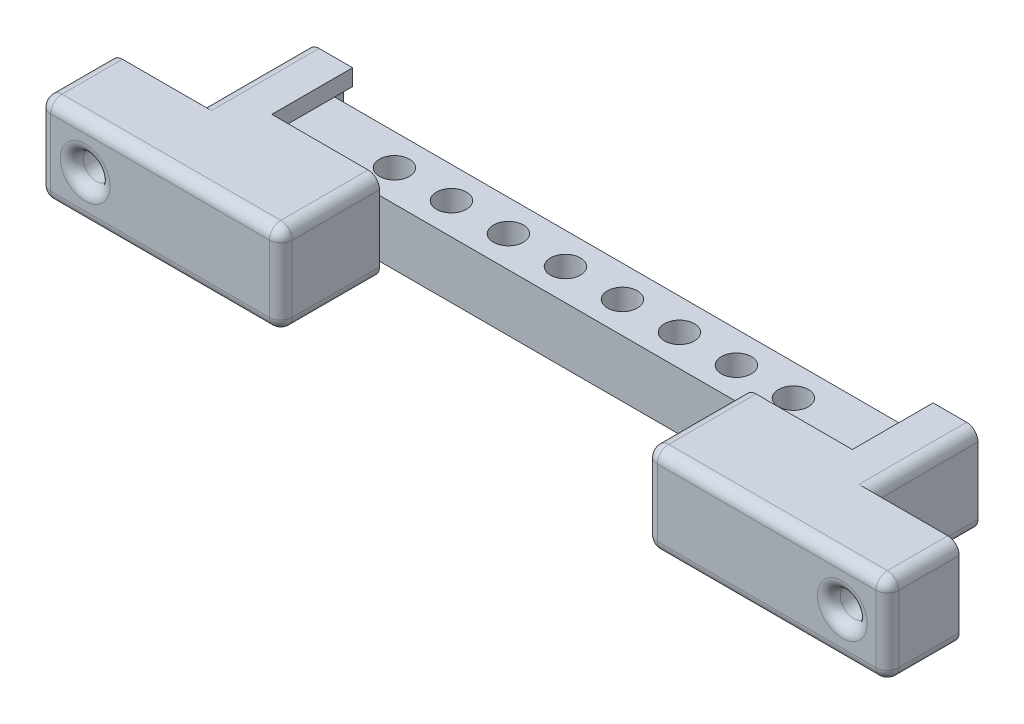
SolidWorks part; units mm, degrees
ref_plane "Front Plane" through (0, 0, 0) normal (0, 0, 1) x (1, 0, 0)
ref_plane "Top Plane" through (0, 0, 0) normal (0, 1, 0) x (1, 0, 0)
ref_plane "Right Plane" through (0, 0, 0) normal (1, 0, 0) x (0, 0, -1)
sketch "Sketch1" plane through (0, 0, 0) normal (0, 1, 0) x (1, 0, 0)
  line L0 (47.244, 0) -> (-47.244, 0)
  line L5 (-47.244, 0) -> (-47.244, 8)
  line L6 (-47.244, 8) -> (-37.338, 8)
  line L7 (-37.338, 8) -> (-37.338, 20)
  line L8 (-37.338, 20) -> (-32.338, 20)
  line L9 (-32.338, 20) -> (-32.338, 11)
  line L10 (-32.338, 11) -> (32.338, 11)
  line L11 (0, 0) -> (0, 11) construction
  line L12 (0, 0) -> (0, 22.1755) construction
  line L13 (32.338, 20) -> (32.338, 11)
  line L14 (37.338, 20) -> (32.338, 20)
  line L15 (37.338, 8) -> (37.338, 20)
  line L16 (47.244, 8) -> (37.338, 8)
  line L17 (47.244, 0) -> (47.244, 8)
  dimension "D1" = 94.488
  dimension "D2" = 8
  dimension "D3" = 9.906
  dimension "D4" = 20
  dimension "D5" = 3
  dimension "D6" = 5
extrude "Boss-Extrude1" add sketch "Sketch1" along normal mid plane 10
sketch "Sketch2" plane through (0, 0, -11) normal (0, 0, -1) x (-1, 0, 0)
  line L0 (-32.338, 5) -> (32.338, 5) construction
  line L1 (-20.338, 5) -> (20.338, 5)
  line L2 (-20.338, 5) -> (-20.338, -5)
  line L3 (-20.338, -5) -> (20.338, -5)
  line L4 (20.338, 5) -> (20.338, -5)
  line L5 (-32.338, -5) -> (32.338, -5) construction
  line L6 (-32.338, 5) -> (-32.338, -5) construction
  line L7 (32.338, 5) -> (32.338, -5) construction
  dimension "D1" = 12
  dimension "D2" = 12
extrude "Cut-Extrude1" cut sketch "Sketch2" against normal through all
sketch "Sketch3" plane through (0, 0, -8) normal (0, 0, -1) x (-1, 0, 0)
  circle A0 centre (-42.2273, 0) radius 1.5
  circle A1 centre (42.1322, 0) radius 1.5
  circle A2 centre (-42.2273, 0) radius 3.5
  circle A3 centre (42.1322, 0) radius 3.5
  dimension "D1" = 3
  dimension "D2" = 2
extrude "Cut-Extrude2" cut sketch "Sketch3" against normal through all contours A1 | A0 region at (42.2273, 0, -8) region at (-42.1322, 0, -8)
extrude "Cut-Extrude3" cut sketch "Sketch3<3>" against normal blind 3 contours A2 A0 | A3 region at (45.6284, 0, -8)
sketch "Sketch3<3>" plane through (0, 0, -8) normal (0, 0, -1) x (-1, 0, 0) same geometry as "Sketch3"
sketch "Sketch5" plane through (0, 0, -20) normal (0, 0, -1) x (-1, 0, 0)
  line L0 (-32.338, 5) -> (-32.338, -5) construction
  line L1 (33.338, -3.175) -> (-33.338, -3.175)
  line L2 (33.338, -3.175) -> (33.338, 3.175)
  line L3 (33.338, 3.175) -> (-33.338, 3.175)
  line L4 (-33.338, -3.175) -> (-33.338, 3.175)
  line L5 (33.338, -3.175) -> (-33.338, 3.175) construction
  line L6 (33.338, 3.175) -> (-33.338, -3.175) construction
  point P0 (0, 0)
  dimension "D1" = 1
  dimension "D2" = 6.35
extrude "Cut-Extrude4" cut sketch "Sketch5" against normal up to surface (9 mm away) up to face at (26.338, 0, -11)
sketch "Sketch6" plane through (0, 0, -11) normal (0, 0, -1) x (-1, 0, 0)
  line L1 (-33.338, 3.175) -> (33.338, 3.175)
  line L2 (-33.338, 3.175) -> (-33.338, -3.175)
  line L3 (-33.338, -3.175) -> (33.338, -3.175)
  line L4 (33.338, 3.175) -> (33.338, -3.175)
extrude "Boss-Extrude2" add sketch "Sketch6" along normal offset from surface (7 mm away) 2 separate body up to face at (33.838, 0, -20)
sketch "Sketch7" plane through (0, -3.175, 0) normal (0, -1, 0) x (1, 0, 0)
  line L0 (0, -18) -> (0, -11) construction
  line L1 (-33.338, -18) -> (33.338, -18) construction
  line L2 (33.338, -11) -> (-33.338, -11) construction
  line L3 (0, -14.5) -> (-32.338, -14.5) construction
  line L4 (-32.338, -11) -> (-32.338, -20) construction
  line L5 (0, -14.5) -> (32.338, -14.5) construction
  line L6 (32.338, -20) -> (32.338, -11) construction
  circle A0 centre (-22.178, -14.5) radius 1.6707
  circle A1 centre (-15.828, -14.5) radius 1.6707
  circle A2 centre (-9.478, -14.5) radius 1.6707
  circle A3 centre (-3.128, -14.5) radius 1.6707
  circle A4 centre (3.222, -14.5) radius 1.6707
  circle A5 centre (9.572, -14.5) radius 1.6707
  circle A6 centre (15.922, -14.5) radius 1.6707
  circle A7 centre (22.272, -14.5) radius 1.6707
  dimension "D1" = 10.16
  dimension "D2" = 8
extrude "Cut-Extrude5" cut sketch "Sketch7" against normal through all
fillet "Fillet1" radius 1.27 11 edges at (47.244, 0, 0) (33.791, -5, 0) (20.338, 0, 0) (33.791, 5, 0) (40.7273, 0, 0) (47.244, 5, -4) (20.338, -5, -5.5) (20.338, 5, -5.5) (47.244, -5, -4) (37.338, 5, -14) (37.338, -5, -14)
fillet "Fillet2" radius 1.27 11 edges at (-47.244, 0, 0) (-33.791, 5, 0) (-20.338, 0, 0) (-33.791, -5, 0) (-43.6322, 0, 0) (-20.338, 5, -5.5) (-20.338, -5, -5.5) (-37.338, -5, -14) (-37.338, 5, -14) (-47.244, 5, -4) (-47.244, -5, -4)
